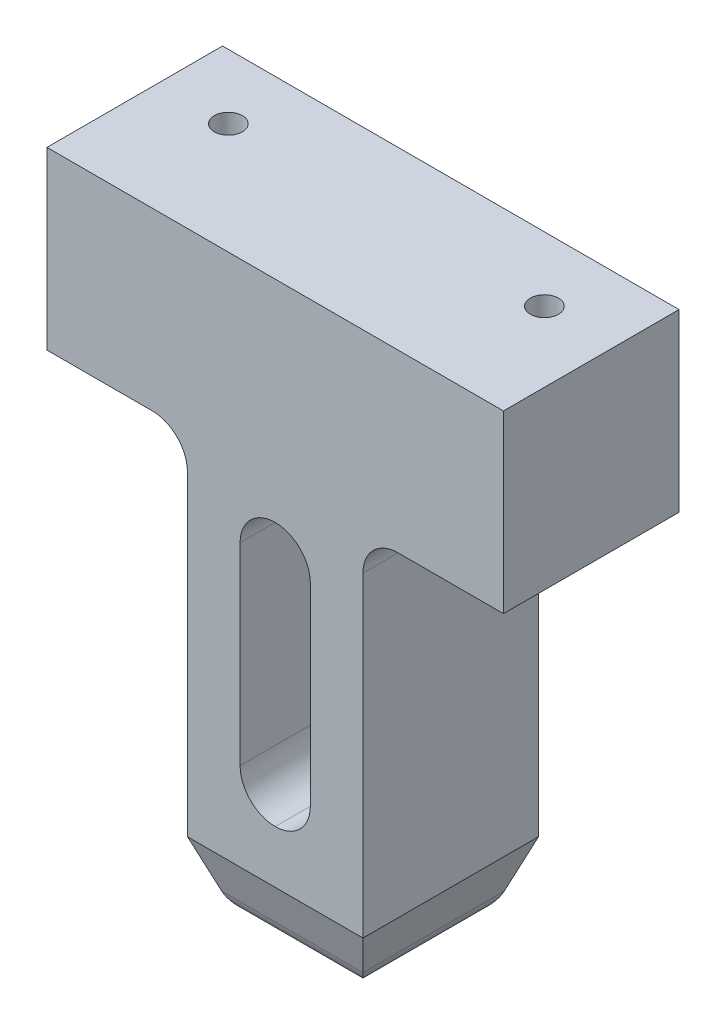
SolidWorks part; units mm, degrees
ref_plane "Front Plane" through (0, 0, 0) normal (0, 0, 1) x (1, 0, 0)
ref_plane "Top Plane" through (0, 0, 0) normal (0, 1, 0) x (1, 0, 0)
ref_plane "Right Plane" through (0, 0, 0) normal (1, 0, 0) x (0, 0, -1)
sketch "Sketch1" plane through (0, 0, 0) normal (1, 0, 0) x (0, 0, -1)
  line L0 (0, 0) -> (0, 5) construction
  line L8 (-5, 5) -> (5, 5)
  line L9 (-5, 5) -> (-5, -5)
  line L10 (-5, -5) -> (5, -5)
  line L11 (5, 5) -> (5, -5)
  line L12 (-5, 5) -> (5, -5) construction
  line L13 (-5, -5) -> (5, 5) construction
  dimension "D1" = 10
  dimension "D2" = 10
extrude "Boss-Extrude1" add sketch "Sketch1" along normal blind 26
sketch "Sketch2" plane through (0, 5, -8.0472) normal (0, -1, 0) x (1, 0, 0)
  line L0 (0, 6.716) -> (26, 6.716) construction
  line L3 (4, 6.716) -> (22, 6.716)
  point P9 (13, 6.716)
sketch "Sketch3" plane through (0, 5, -8.0472) normal (0, -1, 0) x (1, 0, 0)
  circle A0 centre (4, 6.716) radius 0.8
  circle A1 centre (22, 6.716) radius 0.8
extrude "Cut-Extrude1" cut sketch "Sketch3" along normal blind 7
sketch "Sketch4" plane through (0, -5, 0) normal (0, -1, 0) x (1, 0, 0)
  line L0 (26, 0) -> (0, 0) construction
  line L1 (26, 5) -> (26, -5) construction
  line L2 (0, 5) -> (0, -5) construction
  line L3 (26, -5) -> (0, -5) construction
  line L4 (18, 5) -> (8, 5)
  line L5 (18, 5) -> (18, -5)
  line L6 (18, -5) -> (8, -5)
  line L7 (8, 5) -> (8, -5)
  line L8 (18, 5) -> (8, -5) construction
  line L9 (18, -5) -> (8, 5) construction
  point P6 (13, 0)
  dimension "D1" = 10
extrude "Boss-Extrude2" add sketch "Sketch4" along normal blind 20
sketch "Sketch5" plane through (0, 0, 5) normal (0, 0, 1) x (1, 0, 0)
  line L0 (18, -25) -> (8, -25) construction
  line L4 (8, -25) -> (8, -5) construction
  line L5 (15, -7) -> (11, -7)
  line L6 (15, -7) -> (15, -22)
  line L7 (15, -22) -> (11, -22)
  line L8 (11, -7) -> (11, -22)
  line L9 (18, -25) -> (18, -5) construction
  line L10 (26, -5) -> (18, -5) construction
  point P6 (12.8423, -17.8859)
  dimension "D1" = 3
  dimension "D2" = 3
  dimension "D3" = 3
  dimension "D4" = 2
extrude "Cut-Extrude2" cut sketch "Sketch5" against normal blind 20
sketch "Sketch6" plane through (0, -25, 0) normal (0, -1, 0) x (1, 0, 0)
  line L1 (18, 5) -> (8, 5)
  line L2 (18, 5) -> (18, -5)
  line L3 (18, -5) -> (8, -5)
  line L4 (8, 5) -> (8, -5)
extrude "Boss-Extrude3" add sketch "Sketch6" along normal blind 4 draft 20 separate body
fillet "Fillet2" radius 2 4 edges at (15, -7, 0) (11, -7, 0) (15, -22, 0) (11, -22, 0)
fillet "Fillet5" radius 2 2 edges at (18, -5, 0) (8, -5, 0)
fillet "Fillet8" radius 2 4 edges at (13, -29, -3.5441) (9.4559, -29, 0) (13, -29, 3.5441) (16.5441, -29, 0)
